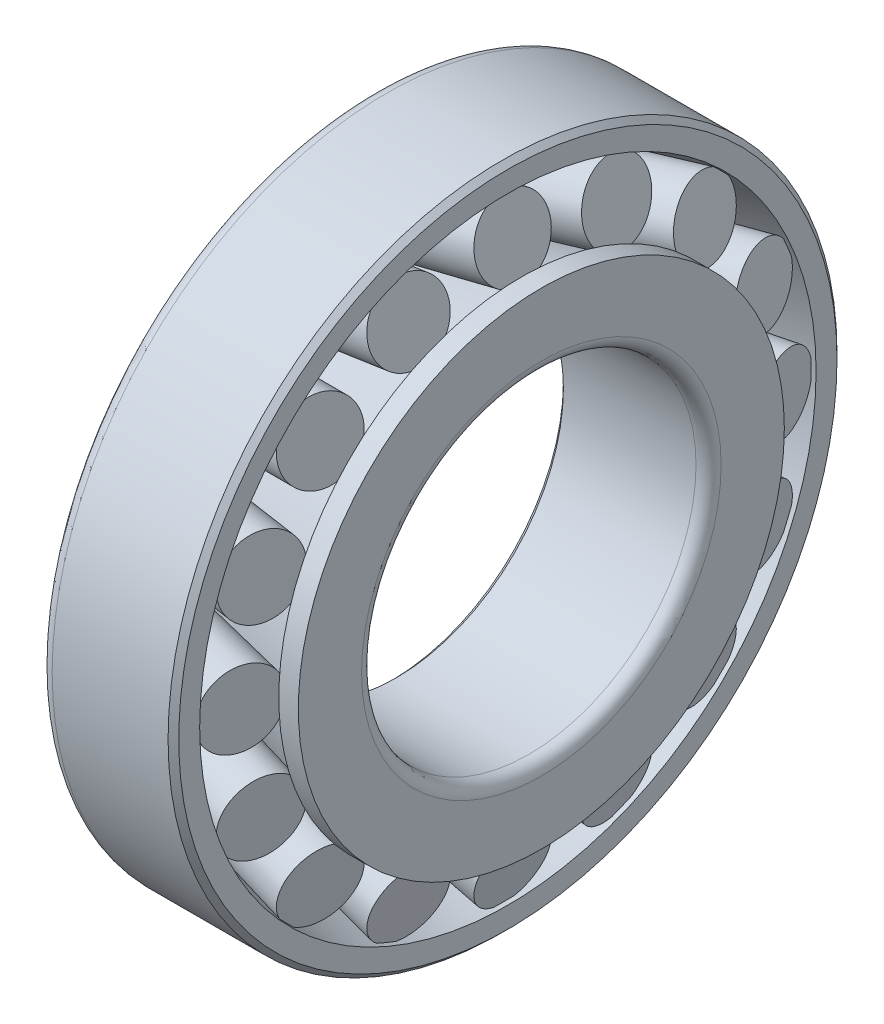
SolidWorks part; units mm, degrees
ref_plane "Plane1" through (0, 0, 0) normal (0, 0, 1) x (1, 0, 0)
ref_plane "Plane2" through (0, 0, 0) normal (0, 1, 0) x (1, 0, 0)
ref_plane "Plane3" through (0, 0, 0) normal (1, 0, 0) x (0, 0, -1)
sketch "Clipboard" plane through (0, 0, 0) normal (0, 0, 1) x (1, 0, 0)
  line L0 (0, 0) -> (10, 0) construction
  line L1 (0, 0) -> (63.1837, -18.1176)
  line L2 (0, 0) -> (38.4505, 11.0255)
  line L3 (0, 0) -> (76.9009, -22.051)
  line L4 (0, 0) -> (-14.3978, -0.2513)
  line L5 (0, 0) -> (-9, 20)
  dimension "Bore" = 40
  dimension "Count" = 16
  dimension "Show_count" = 16
  dimension "Max_count" = 16
  dimension "Min_count" = 1
  dimension "Race_OD" = 80
  dimension "Race_ID" = 65.73
  dimension "cyl_len" = 14.4
  dimension "Roller_diameter" = 9
  dimension "OA_width" = 20
sketch "OutRacSke" plane through (0, 0, 0) normal (0, 0, 1) x (1, 0, 0)
  line L0 (-4, 36.8602) -> (-20, 32.865)
  line L1 (-20, 32.865) -> (-20, 38.5)
  line L2 (-18.5, 40) -> (-4.64, 40)
  line L3 (-4.64, 40) -> (-4, 39.36)
  line L4 (-4, 39.36) -> (-4, 36.8602)
  line L5 (-42.5, 0) -> (42.5, 0) construction
  arc A0 (-20, 38.5) -> (-18.5, 40) centre (-18.5, 38.5) cw
  dimension "cup_radius" = 1.5
  dimension "OD" = 80
  dimension "cup_width" = 16
  dimension "Tangle" = 14.02
  dimension "offset" = 20
  dimension "chamfer" = 0.64
  dimension "D8" = 45
  dimension "cup_SID" = 65.73
revolve "OuterRace" add sketch "OutRacSke" angle 360 about L5
sketch "RolDetSke" plane through (0, 0, 0) normal (0, 0, 1) x (1, 0, 0)
  line L0 (-17.4098, 29.0398) -> (-18.5, 33.4057)
  line L1 (-17.4098, 29.0398) -> (-3.4388, 32.5283)
  line L2 (-4.529, 36.8943) -> (-3.4388, 32.5283)
  line L4 (-41.8866, 22.928) -> (7.9945, 35.3832) construction
  line L5 (-4.529, 36.8943) -> (-18.5, 33.4057)
  line L9 (-4, 36.8602) -> (-20, 32.865) construction
  dimension "cyl_len" = 14.4
  dimension "D2" = 18.5
  dimension "Roller_diameter" = 9
  dimension "dy" = 33.4057
revolve "RollerDetailed" add sketch "RolDetSke" angle 360 about L4
sketch "RolSimSke" plane through (0, 0, 0) normal (0, 0, 1) x (1, 0, 0)
  line L0 (0, 0) -> (-32, 0) construction
  line L1 (-18.5, 33.4057) -> (-4.529, 36.8943)
  line L2 (-18.5, 33.4057) -> (-16.3197, 24.6738)
  line L3 (-16.3197, 24.6738) -> (-2.3486, 28.1624)
  line L4 (-4.529, 36.8943) -> (-2.3486, 28.1624)
  dimension "Roller_diameter" = 9
  dimension "Cyl_Len" = 14.4
  dimension "dx" = 18.5
  dimension "dy" = 33.4057
  dimension "Tangle" = 14.02
revolve "RollersSimplified" [suppressed] add sketch "RolSimSke" angle 360 about L0
ref_axis "Axis1" through (-50, 0, 0) along (1, 0, 0)
pattern_circular "RollersDetailed" count 16 every 22.5 about axis through (-50, 0, 0) along (1, 0, 0) of "RollerDetailed", "OuterRace"
sketch "InsRacSke" plane through (0, 0, 0) normal (0, 0, 1) x (1, 0, 0)
  line L0 (-16.4211, 25.1238) -> (-18, 25.1238)
  line L1 (-20, 38.5) -> (-20, -38.5) construction
  line L2 (-18, 25.1238) -> (-18, 20.64)
  line L3 (-18, 20.64) -> (-17.36, 20)
  line L4 (-17.36, 20) -> (-1.5, 20)
  line L5 (0, 21.5) -> (0, 29.0624)
  line L6 (0, 29.0624) -> (-2.3377, 29.0624)
  line L7 (-2.3377, 29.0624) -> (-2.3377, 28.1624)
  line L8 (-2.3377, 28.1624) -> (-16.3088, 24.6738)
  line L9 (-16.3088, 24.6738) -> (-16.4211, 25.1238)
  line L10 (-42.5, 0) -> (42.5, 0) construction
  arc A0 (-1.5, 20) -> (0, 21.5) centre (-1.5, 21.5) ccw
  dimension "cone_radius" = 1.5
  dimension "Bore" = 40
  dimension "D2" = 20
  dimension "cone_width" = 18
  dimension "Tangle" = 14.02
  dimension "cyl_len" = 14.4
  dimension "dy" = 24.6738
  dimension "dx" = 16.3088
  dimension "chamfer" = 0.64
  dimension "D11" = 45
  dimension "front_groove" = 0.45
  dimension "Groove_dp" = 0.9
revolve "InnerRace" add sketch "InsRacSke" angle 360 about L10
sketch "CagSpiSke" plane through (0, 0, 0) normal (0, 0, 1) x (1, 0, 0)
  line L3 (-2.7402, 32.5366) -> (-17.4098, 28.8736)
  line L4 (-17.8466, 28.1461) -> (-17.5559, 26.9819)
  line L6 (-42.5, 0) -> (42.5, 0) construction
  arc A1 (-17.4098, 28.8736) -> (-17.8466, 28.1461) centre (-17.2645, 28.2915) ccw
  dimension "radius" = 0.6
  dimension "Tangle" = 14.02
  dimension "offset" = 1.8
  dimension "dx" = 17.4098
  dimension "dy" = 28.8736
  dimension "length" = 15.12
revolve "CageSpine" [suppressed] add sketch "CagSpiSke" angle 0.001 about L6
equation "\"OD@OutRacSke\" = \"Race_OD@Clipboard\""
equation "\"cup_SID@OutRacSke\" = \"Race_ID@Clipboard\""
equation "\"chamfer@OutRacSke\" = \"cup_width@OutRacSke\" / 25"
equation "\"offset@OutRacSke\" = \"OA_width@Clipboard\""
equation "\"D2@RolDetSke\" = \"offset@OutRacSke\" - \"cup_radius@OutRacSke\""
equation "\"dy@RolDetSke\" =  ( ( \"Race_ID@Clipboard\" / 2 ) + ( \"cup_radius@OutRacSke\" ) * tan(\"Tangle@OutRacSke\" * 3.141592654/180) ) * 1.005"
equation "\"cyl_len@RolDetSke\" = \"cyl_len@Clipboard\""
equation "\"Roller_diameter@RolDetSke\" = \"Roller_diameter@Clipboard\""
equation "\"Dx@RolSimSke\" = \"offset@OutRacSke\" - \"cup_radius@OutRacSke\""
equation "\"dy@RolSimSke\" =  ( ( \"Race_ID@Clipboard\" / 2 ) + ( \"cup_radius@OutRacSke\" ) * tan(\"Tangle@OutRacSke\" * 3.141592654/180) ) * 1.005"
equation "\"cyl_len@RolSimSke\" = \"cyl_len@Clipboard\""
equation "\"Roller_diameter@RolSimSke\" = \"Roller_diameter@Clipboard\""
equation "\"Bore@InsRacSke\" = \"Bore@Clipboard\""
equation "\"Tangle@InsRacSke\" = \"Tangle@OutRacSke\""
equation "\"cyl_len@InsRacSke\" = \"cyl_len@Clipboard\""
equation "\"chamfer@InsRacSke\" = \"chamfer@OutRacSke\""
equation "\"d2@InsRacSke\" = \"OA_width@Clipboard\""
equation "\"dx@InsRacSke\" = \"offset@OutRacSke\" - \"cup_radius@OutRacSke\" -  (  \"Roller_diameter@Clipboard\" * 1.005 )  * sin(\"Tangle@InsRacSke\" * 3.141592654/180)"
equation "\"dy@InsRacSke\" = ( ( \"Race_ID@Clipboard\" / 2 ) + ( \"cup_radius@OutRacSke\" ) * tan(\"Tangle@OutRacSke\" * 3.141592654/180) ) * 1.005 -  ( \"Roller_diameter@Clipboard\" )  * cos(\"Tangle@InsRacSke\" * 3.141592654/180) "
equation "\"front_groove@InsRacSke\" = \"Groove_dp@InsRacSke\" / 2"
equation "\"Tangle@CagSpiSke\" = \"Tangle@OutRacSke\""
equation "\"dx@CagSpiSke\" = ( \"offset@OutRacSke\" - \"cup_radius@OutRacSke\" ) -  (  \"Roller_diameter@Clipboard\" / 2  )  * sin(\"Tangle@InsRacSke\" * 3.141592654/180)"
equation "\"dy@CagSpiSke\" = ( ( \"Race_ID@Clipboard\" / 2 ) + ( \"cup_radius@OutRacSke\" ) * tan(\"Tangle@OutRacSke\" * 3.141592654/180) )  -  ( \"Roller_diameter@Clipboard\" / 2 )  * cos(\"Tangle@InsRacSke\" * 3.141592654/180) "
equation "\"length@CagSpiSke\" = \"cyl_len@Clipboard\" * 1.05"
equation "\"offset@CagSpiSke\" = \"Roller_diameter@Clipboard\" / 5"
equation "\"radius@CagSpiSke\" = \"offset@CagSpiSke\" / 3"
equation "\"D3@CageSpine\" = \"Roller_diameter@Clipboard\" / 6"
equation "\"Max_count@Clipboard\" = int( 3.14159265 / atn(( \"Roller_diameter@Clipboard\" / 2) / sqr( \"dy@CagSpiSke\"  *  \"dy@CagSpiSke\" - ( \"Roller_diameter@Clipboard\" / 2) *  ( \"Roller_diameter@Clipboard\" / 2))))"
equation "\"Max_count@Clipboard\" = ((sgn( \"Max_count@Clipboard\" - \"Count@Clipboard\" )-1)*( \"Max_count@Clipboard\" - \"Count@Clipboard\" ))/-2+ \"Count@Clipboard\""
equation "\"Count@RollersDetailed\" = int( \"Show_count@Clipboard\" ) "
equation "\"Count@RollersDetailed\" = ((sgn( \"Count@RollersDetailed\" - \"Max_count@Clipboard\" )-1)*( \"Count@RollersDetailed\" - \"Max_count@Clipboard\" ))/-2+ \"Max_count@Clipboard\""
equation "\"Count@RollersDetailed\" = ((sgn( \"Count@RollersDetailed\" - \"Min_count@Clipboard\" )+1)*( \"Count@RollersDetailed\" - \"Min_count@Clipboard\"))/2 +\"Min_count@Clipboard\""
equation "\"Angle@RollersDetailed\" = 360.0 / \"Max_count@Clipboard\""
equation "\"Angle@CageSpine\" =  \"Angle@RollersDetailed\" * ( \"Count@RollersDetailed\" -1 + int( \"Count@RollersDetailed\" / \"Max_count@Clipboard\" ) )  + 0.001 -  int( \"Count@RollersDetailed\" / \"Max_count@Clipboard\" ) * 0.001"
equation "\"Angle@CageSpine\" =  \"Angle@CageSpine\" * int( \"Min_count@Clipboard\" / 2) + int(1 / \"Min_count@Clipboard\")  * 0.001"
equation "\"Tangle@RolSimSke\" = \"Tangle@OutRacSke\""
